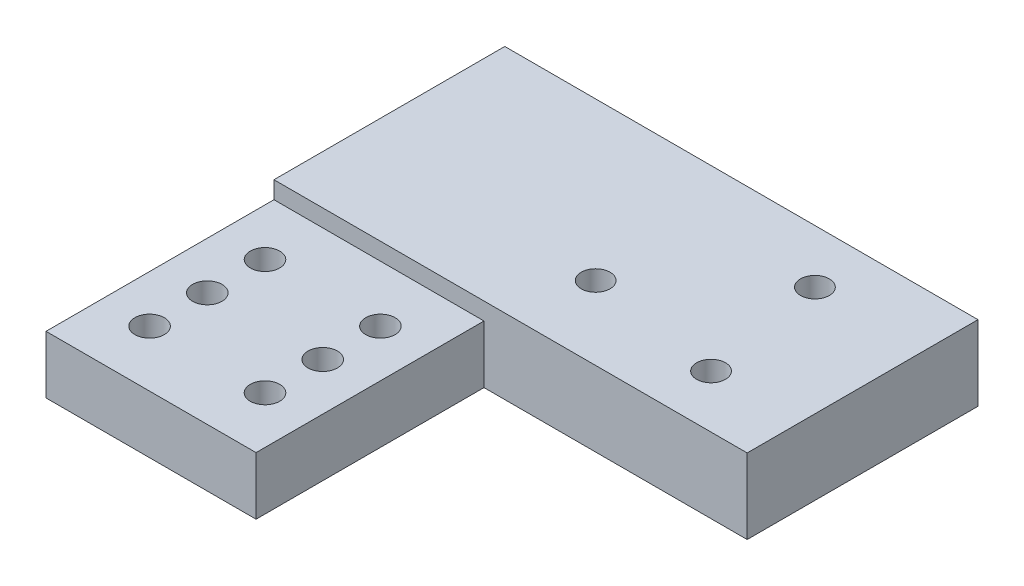
SolidWorks part; units mm, degrees
ref_plane "Front Plane" through (0, 0, 0) normal (0, 0, 1) x (1, 0, 0)
ref_plane "Top Plane" through (0, 0, 0) normal (0, 1, 0) x (1, 0, 0)
ref_plane "Right Plane" through (0, 0, 0) normal (1, 0, 0) x (0, 0, -1)
sketch "Sketch1" plane through (0, 0, 0) normal (0, 1, 0) x (1, 0, 0)
  line L1 (0, 0) -> (36.4, 0)
  line L2 (0, 0) -> (0, 39.5)
  line L3 (0, 39.5) -> (36.4, 39.5)
  line L4 (36.4, 0) -> (36.4, 39.5)
  circle A0 centre (8.2, 29.75) radius 2.55
  circle A1 centre (28.2, 29.75) radius 2.55
  circle A2 centre (28.2, 19.75) radius 2.55
  circle A3 centre (28.2, 9.75) radius 2.55
  circle A4 centre (8.2, 19.75) radius 2.55
  circle A5 centre (8.2, 9.75) radius 2.55
  dimension "D3" = 5.1
  dimension "D1" = 8.2
  dimension "D2" = 9.75
  dimension "D4" = 8.2
  dimension "D5" = 9.75
  dimension "D8" = 20
  dimension "D9" = 39.5
  dimension "D6" = 2
  dimension "D7" = 3
extrude "Boss-Extrude1" add sketch "Sketch1" along normal blind 10
sketch "Sketch2" plane through (0, 10, 0) normal (0, 1, 0) x (1, 0, 0)
  line L1 (0, 39.5) -> (82, 39.5)
  line L2 (0, 39.5) -> (0, 79.5)
  line L3 (0, 79.5) -> (82, 79.5)
  line L4 (82, 39.5) -> (82, 79.5)
  dimension "D1" = 82
  dimension "D2" = 40
extrude "Boss-Extrude2" add sketch "Sketch2" against normal blind 10 and the other way blind 3
sketch "Sketch4" plane through (0, 13, 0) normal (0, 1, 0) x (1, 0, 0)
  line L0 (66.5819, 48.6599) -> (66.5819, 39.5)
  line L2 (66.5819, 39.5) -> (82, 39.5)
  point P2 (0, 0)
  dimension "D1" = 9.1599
  dimension "D2" = 15.4181
  dimension "D3" = 0
  dimension "D4" = 0
  dimension "D5" = 15.4181
sketch "Sketch3" plane through (0, 13, 0) normal (0, 1, 0) x (1, 0, 0)
  line L7 (42.9961, 52.2457) -> (66.5819, 52.2457)
  line L8 (66.5819, 48.6599) -> (42.9961, 52.2457)
  line L9 (66.5819, 52.2457) -> (66.5819, 48.6599)
  line L10 (62.9961, 52.2457) -> (42.9961, 52.2457)
  line L11 (62.9961, 70.2457) -> (62.9961, 52.2457)
  line L12 (42.9961, 52.2457) -> (62.9961, 70.2457)
  point P0 (66.5819, 45.0741)
  dimension "D5" = 26.9072
  dimension "D1" = 18
  dimension "D2" = 3.5858
  dimension "D3" = 3.5858
  dimension "D4" = 23.5858
  dimension "D6" = 23.5858
  dimension "D7" = 23.8568
  dimension "D8" = 20
  dimension "D9" = 0
  dimension "D10" = 0
hole_wizard "Ø5.0mm Dowel Hole1" positions "3DSketch1" profile "Sketch5" hole size "Ø5.0" standard "ANSI Metric" end condition through all
sketch3d "3DSketch1"
  point P0 (42.9961, 13, -52.2457)
  point P3 (62.9961, 13, -70.2457)
  point P10 (66.5819, 13, -48.6599)
sketch "Sketch5" plane through (42.9961, 13, -52.2457) normal (1, 0, 0) x (0, 0, 1)
  line L0 (0, 0) -> (0, 13)
  line L1 (0, 13) -> (2.5, 13)
  line L2 (2.5, 13) -> (2.5, 0)
  line L5 (2.5, 0) -> (0, 0)
  line L11 (0, -6.35) -> (0, 107.95) construction
  dimension "Thru Hole Dia." = 5
  dimension "Thru Hole Depth" = 13
